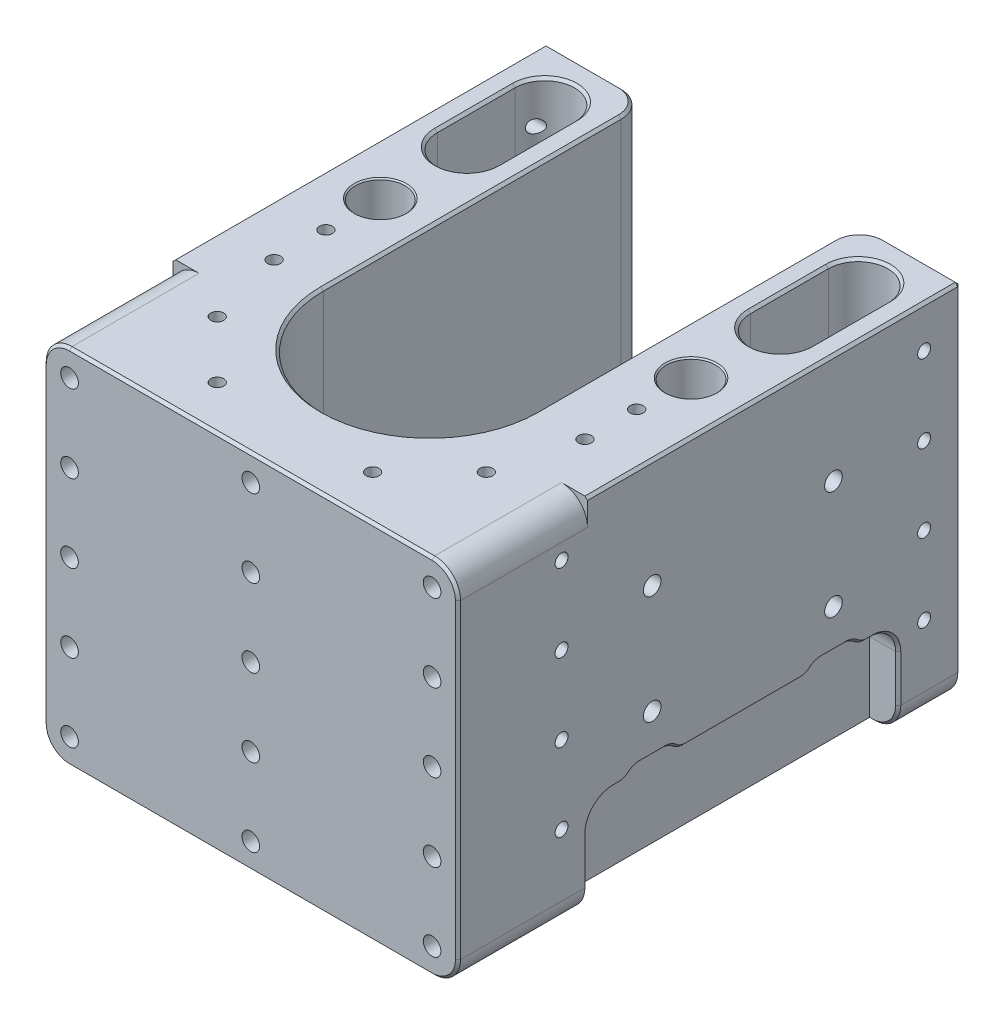
SolidWorks part; units mm, degrees
material "6061-T6 Aluminum"
ref_plane "Front Plane" through (0, 0, 0) normal (0, 0, 1) x (1, 0, 0)
ref_plane "Top Plane" through (0, 0, 0) normal (0, 1, 0) x (1, 0, 0)
ref_plane "Right Plane" through (0, 0, 0) normal (1, 0, 0) x (0, 0, -1)
sketch "Sketch1" plane through (0, 0, 0) normal (0, 1, 0) x (1, 0, 0)
  line L0 (41, 97) -> (80, 97)
  line L1 (-80, -97) -> (80, -97)
  line L2 (-80, -97) -> (-80, 97)
  line L3 (-80, 97) -> (-41, 97)
  line L4 (80, -97) -> (80, 97)
  line L5 (-41, 97) -> (0, 97) construction
  line L6 (0, 97) -> (41, 97) construction
  line L7 (-41, 97) -> (-41, -28)
  line L9 (41, -28) -> (41, 97)
  line L10 (-80, 0) -> (0, 0) construction
  line L11 (0, 0) -> (80, 0) construction
  line L12 (0, -69) -> (0, -97) construction
  arc A2 (-41, -28) -> (41, -28) centre (0, -28) ccw
  point P0 (0, 0)
  dimension "D1" = 160
  dimension "D2" = 194
  dimension "D3" = 28
  dimension "D4" = 82
extrude "Boss-Extrude1" add sketch "Sketch1" along normal blind 140
sketch "Sketch3" plane through (0, 140, 0) normal (0, 1, 0) x (1, 0, 0)
  line L0 (0, 0) -> (0, 13) construction
  line L3 (-60, 13) -> (60, 13) construction
  circle A4 centre (-60, 13) radius 9.55
  circle A5 centre (60, 13) radius 9.55
  dimension "D1" = 13
  dimension "D2" = 120
  dimension "D3" = 19.1
extrude "Cut-Extrude2" cut sketch "Sketch3" against normal blind 14.326 contours A4 | A5 region at (-60, 140, -13) region at (60, 140, -13)
sketch "Sketch8" plane through (80, 0, 0) normal (1, 0, 0) x (0, 0, -1)
  arc A0 (48, 102.25) -> (48, 93.75) centre (48, 98) ccw construction
  arc A1 (-22, 102.25) -> (-22, 93.75) centre (-22, 98) ccw construction
  arc A2 (-22, 60.25) -> (-22, 51.75) centre (-22, 56) ccw construction
  arc A3 (48, 60.25) -> (48, 51.75) centre (48, 56) ccw construction
  arc A4 (48, 102.25) -> (48, 93.75) centre (48, 98) ccw construction
  arc A5 (-22, 102.25) -> (-22, 93.75) centre (-22, 98) ccw construction
  arc A6 (-22, 60.25) -> (-22, 51.75) centre (-22, 56) ccw construction
  arc A7 (48, 60.25) -> (48, 51.75) centre (48, 56) ccw construction
hole_wizard "M8x1.25 Tapped Hole1" positions "Sketch11" profile "Sketch10" tap size "M8x1.25" standard "ANSI Metric"
sketch "Sketch11" plane through (80, 0, 0) normal (1, 0, 0) x (0, 0, -1)
  point P0 (48, 56)
  point P3 (-22, 56)
  point P6 (-22, 98)
  point P9 (48, 98)
cosmetic thread "Hole Thread2" parameters "D1"=25, "D2"=8
cosmetic thread "Hole Thread3" parameters "D1"=25, "D2"=8
cosmetic thread "Hole Thread4" parameters "D1"=25, "D2"=8
cosmetic thread "Hole Thread5" parameters "D1"=25, "D2"=8
sketch "Sketch10" plane through (80, 56, -48) normal (0, 1, 0) x (0, 0, -1)
  line L0 (0, 0) -> (0, 32.0429)
  line L1 (0, 32.0429) -> (3.4, 30)
  line L2 (3.4, 30) -> (3.4, 0)
  line L5 (3.4, 0) -> (0, 0)
  line L10 (0, 32.0429) -> (-3.4, 30) construction
  line L11 (0, -6.35) -> (0, 107.95) construction
  dimension "Tap Drill Dia." = 6.8
  dimension "Tap Drill Depth" = 30
  dimension "Drill Angle" = 118
mirror "Mirror2" about plane through (0, 0, 0) normal (1, 0, 0) of "M8x1.25 Tapped Hole1"
sketch "Sketch33" plane through (0, 0, 97) normal (0, 0, 1) x (1, 0, 0)
  line L0 (-80, 140) -> (-80, 0) construction
  line L1 (-70, 0) -> (70, 0)
  line L2 (-80, 10) -> (-80, 130)
  line L3 (-70, 140) -> (70, 140)
  line L4 (80, 10) -> (80, 130)
  line L5 (-70, 100) -> (-70, 70) construction
  line L6 (-70, 130) -> (-70, 100) construction
  line L7 (-70, 70) -> (-70, 40) construction
  line L8 (-70, 40) -> (-70, 10) construction
  line L9 (-80, 140) -> (80, 140) construction
  arc A0 (-70, 0) -> (-80, 10) centre (-70, 10) cw
  arc A1 (70, 0) -> (80, 10) centre (70, 10) ccw
  arc A2 (70, 140) -> (80, 130) centre (70, 130) cw
  arc A3 (-80, 130) -> (-70, 140) centre (-70, 130) cw
  circle A4 centre (-70, 130) radius 3.375
  circle A5 centre (-70, 100) radius 3.375
  circle A7 centre (-70, 70) radius 3.375
  circle A8 centre (-70, 10) radius 3.375
  circle A9 centre (-70, 40) radius 3.375
  circle A10 centre (0, 130) radius 3.375
  circle A11 centre (70, 130) radius 3.375
  circle A12 centre (0, 100) radius 3.375
  circle A13 centre (70, 100) radius 3.375
  circle A14 centre (0, 70) radius 3.375
  circle A15 centre (70, 70) radius 3.375
  circle A16 centre (0, 40) radius 3.375
  circle A17 centre (70, 40) radius 3.375
  circle A18 centre (70, 10) radius 3.375
  circle A19 centre (0, 10) radius 3.375
  dimension "D2" = 10
  dimension "D3" = 6.75
fillet "Fillet1" radius 10 2 edges at (41, 70, -97) (-41, 70, -97)
sketch "Sketch36" plane through (0, 0, 0) normal (0, 1, 0) x (1, 0, 0)
  line L0 (-69, 13) -> (0, 13) construction
  line L1 (-102.762, 73) -> (-69, 73)
  line L2 (-102.762, 73) -> (-102.762, -47)
  line L3 (-102.762, -47) -> (-69, -47)
  line L4 (-69, 73) -> (-69, -47)
  line L5 (122.5295, 73) -> (69, 73)
  line L6 (122.5295, 73) -> (122.5295, -47)
  line L7 (122.5295, -47) -> (69, -47)
  line L8 (69, 73) -> (69, -47)
  line L9 (0, 13) -> (69, 13) construction
  line L10 (-80, -18.6) -> (-80, -25.4) construction
  line L11 (-80, 51.4) -> (-80, 44.6) construction
  line L12 (-80, -18.6) -> (-80, -25.4) construction
  line L13 (-80, 51.4) -> (-80, 44.6) construction
  line L14 (-80, 44.6) -> (-69, 13) construction
  line L15 (-69, 13) -> (-80, -18.6) construction
  line L16 (0, 13) -> (0, 0) construction
  dimension "D1" = 138
  dimension "D2" = 120
extrude "Cut-Extrude3" cut sketch "Sketch36" along normal blind 38
hole_wizard "CBORE for M8 SHCS1" positions "Sketch31" profile "Sketch32" counterbore size "M8" standard "ANSI Metric" end condition through all
sketch "Sketch31" plane through (0, 0, 0) normal (0, -1, 0) x (-1, 0, 0)
  circle A4 centre (60, 13) radius 9.55 construction
  circle A5 centre (-60, 13) radius 9.55 construction
  point P0 (60, 13)
  point P2 (-60, 13)
sketch "Sketch32" plane through (-60, 0, -13) normal (1, 0, 0) x (0, 0, -1)
  line L0 (0, 0) -> (0, 140)
  line L1 (0, 140) -> (4.5, 140)
  line L3 (4.5, 140) -> (4.5, 9)
  line L4 (4.5, 9) -> (7.5, 9)
  line L5 (7.5, 9) -> (7.5, 0)
  line L7 (7.5, 0) -> (0, 0)
  line L11 (0, -6.35) -> (0, 107.95) construction
  dimension "Thru Hole Dia." = 9
  dimension "Thru Hole Depth" = 140
  dimension "C'Bore Dia." = 15
  dimension "C'Bore Depth" = 9
chamfer "Chamfer7" distance 0.5 angle 45 2 edges at (60, 140, -3.45) (-60, 140, -3.45)
chamfer "Chamfer11" distance 1 angle 45 2 edges at (60, 0, -20.5) (-60, 0, -20.5)
chamfer "Chamfer12" distance 0.5 angle 45 4 edges at (-60, 9, -17.5) (60, 9, -17.5) (-60, 125.674, -8.5) (60, 125.674, -8.5)
sketch "Sketch38" plane through (0, 0, 0) normal (0, -1, 0) x (1, 0, 0)
  circle A0 centre (54, 32.5) radius 4.25 construction
  circle A1 centre (54, 2.5) radius 4.25 construction
  circle A2 centre (54, -27.5) radius 4.25 construction
  circle A3 centre (54, -57.5) radius 4.25 construction
  circle A4 centre (-54, -57.5) radius 4.25 construction
  circle A5 centre (-54, -27.5) radius 4.25 construction
  circle A6 centre (-54, 2.5) radius 4.25 construction
  circle A7 centre (-54, 32.5) radius 4.25 construction
  circle A8 centre (54, 32.5) radius 4.25
  circle A9 centre (54, 2.5) radius 4.25
  circle A10 centre (54, -27.5) radius 4.25
  circle A11 centre (54, -57.5) radius 4.25
  circle A12 centre (-54, -57.5) radius 4.25
  circle A13 centre (-54, -27.5) radius 4.25
  circle A14 centre (-54, 2.5) radius 4.25
  circle A15 centre (-54, 32.5) radius 4.25
sketch "Sketch39" plane through (0, 0, 0) normal (0, -1, 0) x (-1, 0, 0)
  line L0 (-54, -2.5) -> (-54, -32.5) construction
  line L1 (-54, -32.5) -> (-54, -62.5) construction
  line L3 (54, -2.5) -> (54, -32.5) construction
  line L4 (54, -32.5) -> (54, -62.5) construction
  point P0 (54, 57.5)
  point P3 (54, 27.5)
  point P6 (54, -2.5)
  point P9 (54, -32.5)
  point P12 (-54, 57.5)
  point P15 (-54, 27.5)
  point P18 (-54, -2.5)
  point P21 (-54, -32.5)
  point P36 (-54, -62.5)
  point P39 (54, -62.5)
hole_wizard "M8x1.25 Tapped Hole3" positions "Sketch39" profile "Sketch40" tap size "M8x1.25" standard "ANSI Metric"
sketch "Sketch40" plane through (-54, 0, -57.5) normal (1, 0, 0) x (0, 0, -1)
  line L0 (0, 0) -> (0, 22.0429)
  line L1 (0, 22.0429) -> (3.4, 20)
  line L2 (3.4, 20) -> (3.4, 0.9)
  line L3 (3.4, 0.9) -> (4.3, 0)
  line L5 (4.3, 0) -> (0, 0)
  line L6 (-3.4, 0.9) -> (-4.3, 0) construction
  line L10 (0, 22.0429) -> (-3.4, 20) construction
  line L11 (0, -6.35) -> (0, 107.95) construction
  dimension "Tap Drill Dia." = 6.8
  dimension "Tap Drill Depth" = 20
  dimension "Near C'Sink Dia." = 8.6
  dimension "Near C'Sink Angle" = 90
  dimension "Drill Angle" = 118
cosmetic thread "Hole Thread36" parameters "D1"=16, "D2"=8
cosmetic thread "Hole Thread37" parameters "D1"=16, "D2"=8
cosmetic thread "Hole Thread38" parameters "D1"=16, "D2"=8
cosmetic thread "Hole Thread39" parameters "D1"=16, "D2"=8
cosmetic thread "Hole Thread40" parameters "D1"=16, "D2"=8
cosmetic thread "Hole Thread41" parameters "D1"=16, "D2"=8
cosmetic thread "Hole Thread42" parameters "D1"=16, "D2"=8
cosmetic thread "Hole Thread43" parameters "D1"=16, "D2"=8
cosmetic thread "Hole Thread85" parameters "D1"=16, "D2"=8
cosmetic thread "Hole Thread86" parameters "D1"=16, "D2"=8
sketch "Sketch41" plane through (0, 0, 0) normal (0, -1, 0) x (1, 0, 0)
  line L0 (-60, 85) -> (-20, 85) construction
  line L1 (-20, 85) -> (20, 85) construction
  line L2 (20, 85) -> (60, 85) construction
  line L3 (0, 85) -> (0, -13) construction
  line L5 (-60, 85) -> (-60, 65.3183) construction
  circle A0 centre (-60, 85) radius 2.5
  circle A1 centre (-20, 85) radius 2.5
  circle A2 centre (20, 85) radius 2.5
  circle A3 centre (60, 85) radius 2.5
  dimension "D2" = 5
  dimension "D1" = 40
  dimension "D3" = 85
sketch "Sketch42" plane through (0, 0, 0) normal (0, -1, 0) x (-1, 0, 0)
sketch "Sketch44" plane through (0, 0, 0) normal (0, -1, 0) x (-1, 0, 0)
  point P0 (-60, -85)
  point P3 (-20, -85)
  point P6 (20, -85)
  point P9 (60, -85)
hole_wizard "M6x1.0 Tapped Hole1" positions "Sketch44" profile "Sketch43" tap size "M6x1.0" standard "ANSI Metric"
sketch "Sketch43" plane through (60, 0, 85) normal (1, 0, 0) x (0, 0, -1)
  line L0 (0, 0) -> (0, 16.5022)
  line L1 (0, 16.5022) -> (2.5, 15)
  line L2 (2.5, 15) -> (2.5, 0.525)
  line L3 (2.5, 0.525) -> (3.025, 0)
  line L5 (3.025, 0) -> (0, 0)
  line L6 (-2.5, 0.525) -> (-3.025, 0) construction
  line L10 (0, 16.5022) -> (-2.5, 15) construction
  line L11 (0, -6.35) -> (0, 107.95) construction
  dimension "Tap Drill Dia." = 5
  dimension "Tap Drill Depth" = 15
  dimension "Near C'Sink Dia." = 6.05
  dimension "Near C'Sink Angle" = 90
  dimension "Drill Angle" = 118
cosmetic thread "Hole Thread44" parameters "D1"=12, "D2"=6
cosmetic thread "Hole Thread45" parameters "D1"=12, "D2"=6
cosmetic thread "Hole Thread46" parameters "D1"=12, "D2"=6
cosmetic thread "Hole Thread47" parameters "D1"=12, "D2"=6
sketch "Sketch45" plane through (0, 140, 0) normal (0, 1, 0) x (1, 0, 0)
  line L0 (-60.5, 47) -> (-60.5, 77) construction
  line L1 (-72, 47) -> (-72, 77)
  line L2 (-49, 47) -> (-49, 77)
  line L3 (-51, 97) -> (-80, 97) construction
  line L4 (-80, 97) -> (-80, -97) construction
  arc A0 (-72, 47) -> (-49, 47) centre (-60.5, 47) ccw
  arc A1 (-49, 77) -> (-72, 77) centre (-60.5, 77) ccw
  point P2 (-60.5, 62)
  dimension "D1" = 20
  dimension "D2" = 19.5
  dimension "D3" = 30
extrude "Cut-Extrude4" cut sketch "Sketch45" against normal blind 25
mirror "Mirror3" about plane through (0, 0, 0) normal (1, 0, 0) of "Cut-Extrude4"
fillet "Fillet2" radius 10 4 edges at (74.5, 38, 47) (74.5, 38, -73) (-74.5, 38, 47) (-74.5, 38, -73)
sketch "Sketch46" plane through (0, 0, 97) normal (0, 0, 1) x (1, 0, 0)
  line L0 (-80, 140) -> (80, 140) construction
  line L1 (80, 140) -> (80, 0) construction
  line L2 (70, 140) -> (80, 140)
  line L3 (80, 140) -> (80, 130)
  arc A0 (70, 140) -> (80, 130) centre (70, 130) cw
  dimension "D1" = 10
extrude "Cut-Extrude5" cut sketch "Sketch46" against normal blind 50
mirror "Mirror4" about plane through (0, 0, 0) normal (1, 0, 0) of "Cut-Extrude5"
fillet "Fillet3" radius 10 4 edges at (-80, 0, -85) (80, 0, -85) (80, 0, 72) (-80, 0, 72)
chamfer "Chamfer3" distance 1 angle 45 28 edges at (80, 140, -25) (80, 70, 97) (-60.5, 0, -97) (-80, 70, 97) (-80, 140, -25) (-65.5, 140, -97) (-80, 75, -97) (0, 140, 97) (60.5, 0, -97) (65.5, 140, -97) (43.9289, 0, -94.0711) (43.9289, 140, -94.0711) (41, 0, -29.5) (41, 140, -29.5) (0, 0, 69) (0, 140, 69) (-41, 0, -29.5) (-41, 140, -29.5) (-43.9289, 0, -94.0711) (-43.9289, 140, -94.0711) (0, 0, 97) (80, 75, -97) (77.0711, 137.0711, 97) (77.0711, 2.9289, 97) (-77.0711, 137.0711, 97) (-77.0711, 2.9289, 97) (77.0711, 2.9289, -97) (-77.0711, 2.9289, -97)
chamfer "Chamfer15" distance 1 angle 45 8 edges at (49, 140, -62) (60.5, 140, -88.5) (60.5, 140, -35.5) (72, 140, -62) (-72, 140, -62) (-60.5, 140, -35.5) (-60.5, 140, -88.5) (-49, 140, -62)
sketch "Sketch55" plane through (69, 0, 0) normal (1, 0, 0) x (0, 0, -1)
  line L0 (63, 38) -> (-37, 38) construction
  line L1 (-32, 30.4123) -> (-12, 30.4123)
  line L2 (-32, 30.4123) -> (-32, 41)
  line L3 (-32, 41) -> (-12, 41)
  line L4 (-12, 30.4123) -> (-12, 41)
  line L5 (-32, 30.4123) -> (-12, 41) construction
  line L6 (-32, 41) -> (-12, 30.4123) construction
  line L7 (38, 30.4123) -> (58, 30.4123)
  line L8 (38, 30.4123) -> (38, 41)
  line L9 (38, 41) -> (58, 41)
  line L10 (58, 30.4123) -> (58, 41)
  line L11 (38, 30.4123) -> (58, 41) construction
  line L12 (38, 41) -> (58, 30.4123) construction
  line L13 (-37, 38) -> (-32, 41) construction
  line L14 (63, 38) -> (58, 41) construction
  point P0 (-22, 35.7062)
  point P5 (48, 35.7062)
  line M9 (63, 38) -> (-37, 38)
  dimension "D1" = 20
  dimension "D2" = 3
  dimension "D3" = 50
extrude "Cut-Extrude6" cut sketch "Sketch55" along normal through all contours L4 L3 L2 M9 | L10 L9 L8 M9 region at (69, 39.5, -48) region at (69, 39.5, 22)
mirror "Mirror6" about plane through (0, 0, 0) normal (1, 0, 0) of "Cut-Extrude6"
fillet "Fillet4" radius 6 8 edges at (74.5, 41, -58) (74.5, 41, -38) (74.5, 41, 32) (74.5, 41, 12) (-74.5, 41, -58) (-74.5, 41, 12) (-74.5, 41, -38) (-74.5, 41, 32)
fillet "Fillet5" radius 6 8 edges at (74.5, 38, -58) (74.5, 38, -38) (74.5, 38, 12) (74.5, 38, 32) (-74.5, 38, -58) (-74.5, 38, -38) (-74.5, 38, 12) (-74.5, 38, 32)
chamfer "Chamfer16" distance 1 angle 45 27 edges at (-69, 0, -13) (69, 0, -13) (-77.0711, 2.9289, -73) (-77.0711, 2.9289, 47) (-80, 19, -73) (-80, 19, 47) (-80, 35.0711, 44.0711) (-80, 38, -61.8706) (-80, 38, 35.8706) (77.0711, 2.9289, -73) (80, 19, -73) (-69.5, 0, -73) (-69.5, 0, 47) (69.5, 0, -73) (-80, 38.3875, 32.6198) (-80, 40.6125, 28.9252) (-80, 41, 22) (-80, 40.6125, 15.0748) (-80, 38.3875, 11.3802) (-80, 38, -13) (-80, 38.3875, -37.3802) (-80, 40.6125, -41.0748) (-80, 41, -48) (-80, 40.6125, -54.9252) (-80, 38.3875, -58.6198) (-80, 35.0711, -70.0711) (80, 35.0711, -70.0711)
hole_wizard "M8x1.25 Tapped Hole4" positions "Sketch47" profile "Sketch48" tap size "M8x1.25" standard "ANSI Metric"
sketch "Sketch47" plane through (0, 0, 97) normal (0, 0, 1) x (1, 0, 0)
  point P0 (-70, 130)
  point P3 (0, 130)
  point P6 (70, 130)
  point P9 (70, 100)
  point P12 (70, 70)
  point P15 (70, 40)
  point P18 (70, 10)
  point P21 (0, 100)
  point P24 (0, 70)
  point P27 (0, 40)
  point P30 (0, 10)
  point P33 (-70, 100)
  point P36 (-70, 70)
  point P39 (-70, 40)
  point P42 (-70, 10)
sketch "Sketch48" plane through (-70, 130, 97) normal (1, 0, 0) x (0, -1, 0)
  line L0 (0, 0) -> (0, 22.0429)
  line L1 (0, 22.0429) -> (3.4, 20)
  line L2 (3.4, 20) -> (3.4, 0)
  line L5 (3.4, 0) -> (0, 0)
  line L10 (0, 22.0429) -> (-3.4, 20) construction
  line L11 (0, -6.35) -> (0, 107.95) construction
  dimension "Tap Drill Dia." = 6.8
  dimension "Tap Drill Depth" = 20
  dimension "Drill Angle" = 118
cosmetic thread "Hole Thread50" parameters "D1"=16, "D2"=8
cosmetic thread "Hole Thread51" parameters "D1"=16, "D2"=8
cosmetic thread "Hole Thread52" parameters "D1"=16, "D2"=8
cosmetic thread "Hole Thread53" parameters "D1"=16, "D2"=8
cosmetic thread "Hole Thread54" parameters "D1"=16, "D2"=8
cosmetic thread "Hole Thread55" parameters "D1"=16, "D2"=8
cosmetic thread "Hole Thread56" parameters "D1"=16, "D2"=8
cosmetic thread "Hole Thread57" parameters "D1"=16, "D2"=8
cosmetic thread "Hole Thread58" parameters "D1"=16, "D2"=8
cosmetic thread "Hole Thread59" parameters "D1"=16, "D2"=8
cosmetic thread "Hole Thread60" parameters "D1"=16, "D2"=8
cosmetic thread "Hole Thread61" parameters "D1"=16, "D2"=8
cosmetic thread "Hole Thread62" parameters "D1"=16, "D2"=8
cosmetic thread "Hole Thread63" parameters "D1"=16, "D2"=8
cosmetic thread "Hole Thread64" parameters "D1"=16, "D2"=8
sketch "Sketch49" plane through (0, 140, 0) normal (0, 1, 0) x (1, 0, 0)
  line L0 (60, -8) -> (60, -28) construction
  line L1 (60, -28) -> (51.9615, -58) construction
  line L2 (51.9615, -58) -> (30, -79.9615) construction
  line L3 (30, -79.9615) -> (0, -88) construction
  circle A0 centre (0, -28) radius 60 construction
  circle A1 centre (0, -88) radius 3
  circle A2 centre (30, -79.9615) radius 3
  circle A3 centre (51.9615, -58) radius 3
  circle A4 centre (60, -28) radius 3
  circle A5 centre (60, -8) radius 3
  circle A6 centre (-30, -79.9615) radius 3
  circle A7 centre (-51.9615, -58) radius 3
  circle A8 centre (-60, -28) radius 3
  circle A9 centre (-60, -8) radius 3
  dimension "D1" = 120
  dimension "D3" = 6
  dimension "D2" = 20
  dimension "D4" = 20
hole_wizard "M6x1.0 Tapped Hole2" positions "Sketch50" profile "Sketch51" tap size "M6x1.0" standard "ANSI Metric"
sketch "Sketch50" plane through (0, 140, 0) normal (0, 1, 0) x (1, 0, 0)
  point P0 (-60, -8)
  point P3 (-60, -28)
  point P6 (-51.9615, -58)
  point P9 (-30, -79.9615)
  point P12 (30, -79.9615)
  point P15 (51.9615, -58)
  point P18 (60, -28)
  point P21 (60, -8)
sketch "Sketch51" plane through (-60, 140, 8) normal (1, 0, 0) x (0, 0, 1)
  line L0 (0, 0) -> (0, 18.5022)
  line L1 (0, 18.5022) -> (2.5, 17)
  line L2 (2.5, 17) -> (2.5, 0)
  line L5 (2.5, 0) -> (0, 0)
  line L10 (0, 18.5022) -> (-2.5, 17) construction
  line L11 (0, -6.35) -> (0, 107.95) construction
  dimension "Tap Drill Dia." = 5
  dimension "Tap Drill Depth" = 17
  dimension "Drill Angle" = 118
cosmetic thread "Hole Thread65" parameters "D1"=12, "D2"=6
cosmetic thread "Hole Thread66" parameters "D1"=12, "D2"=6
cosmetic thread "Hole Thread67" parameters "D1"=12, "D2"=6
cosmetic thread "Hole Thread68" parameters "D1"=12, "D2"=6
cosmetic thread "Hole Thread69" parameters "D1"=12, "D2"=6
cosmetic thread "Hole Thread70" parameters "D1"=12, "D2"=6
cosmetic thread "Hole Thread71" parameters "D1"=12, "D2"=6
cosmetic thread "Hole Thread72" parameters "D1"=12, "D2"=6
sketch "Sketch52" plane through (-80, 0, 0) normal (-1, 0, 0) x (0, 0, 1)
  line L0 (57, 124) -> (57, 94) construction
  line L1 (57, 94) -> (57, 64) construction
  line L2 (57, 64) -> (57, 34) construction
  line L3 (-83, 124) -> (-83, 94) construction
  line L4 (-83, 94) -> (-83, 64) construction
  line L5 (-83, 64) -> (-83, 34) construction
  line L6 (97, 130) -> (97, 10) construction
  line L10 (57, 124) -> (57, 140) construction
  line L11 (47, 140) -> (96, 140) construction
  line L12 (57, 34) -> (57, 4) construction
  line L13 (57, 4) -> (57, -26) construction
  circle A0 centre (-83, 124) radius 3
  circle A1 centre (-83, 94) radius 3
  circle A2 centre (-83, 64) radius 3
  circle A3 centre (-83, 34) radius 3
  circle A4 centre (57, 124) radius 3
  circle A5 centre (57, 94) radius 3
  circle A6 centre (57, 64) radius 3
  circle A7 centre (57, 34) radius 3
  circle A8 centre (57, 4) radius 3
  circle A9 centre (57, -26) radius 3
  circle A10 centre (-83, 4) radius 3
  circle A11 centre (-83, -26) radius 3
  dimension "D1" = 6
  dimension "D2" = 140
  dimension "D3" = 40
  dimension "D4" = 30
  dimension "D5" = 16
hole_wizard "M6x1.0 Tapped Hole3" positions "Sketch53" profile "Sketch54" tap size "M6x1.0" standard "ANSI Metric"
sketch "Sketch53" plane through (-80, 0, 0) normal (-1, 0, 0) x (0, 0, 1)
  point P0 (-83, 124)
  point P3 (-83, 94)
  point P6 (-83, 64)
  point P9 (-83, 34)
  point P12 (57, 124)
  point P15 (57, 94)
  point P18 (57, 64)
  point P21 (57, 34)
sketch "Sketch54" plane through (-80, 124, -83) normal (0, 1, 0) x (0, 0, 1)
  line L0 (0, 0) -> (0, 18.5022)
  line L1 (0, 18.5022) -> (2.5, 17)
  line L2 (2.5, 17) -> (2.5, 0)
  line L5 (2.5, 0) -> (0, 0)
  line L10 (0, 18.5022) -> (-2.5, 17) construction
  line L11 (0, -6.35) -> (0, 107.95) construction
  dimension "Tap Drill Dia." = 5
  dimension "Tap Drill Depth" = 17
  dimension "Drill Angle" = 118
cosmetic thread "Hole Thread73" parameters "D1"=12, "D2"=6
cosmetic thread "Hole Thread74" parameters "D1"=12, "D2"=6
cosmetic thread "Hole Thread75" parameters "D1"=12, "D2"=6
cosmetic thread "Hole Thread76" parameters "D1"=12, "D2"=6
cosmetic thread "Hole Thread77" parameters "D1"=12, "D2"=6
cosmetic thread "Hole Thread78" parameters "D1"=12, "D2"=6
cosmetic thread "Hole Thread79" parameters "D1"=12, "D2"=6
cosmetic thread "Hole Thread80" parameters "D1"=12, "D2"=6
mirror "Mirror5" about plane through (0, 0, 0) normal (1, 0, 0) of "M6x1.0 Tapped Hole3"
